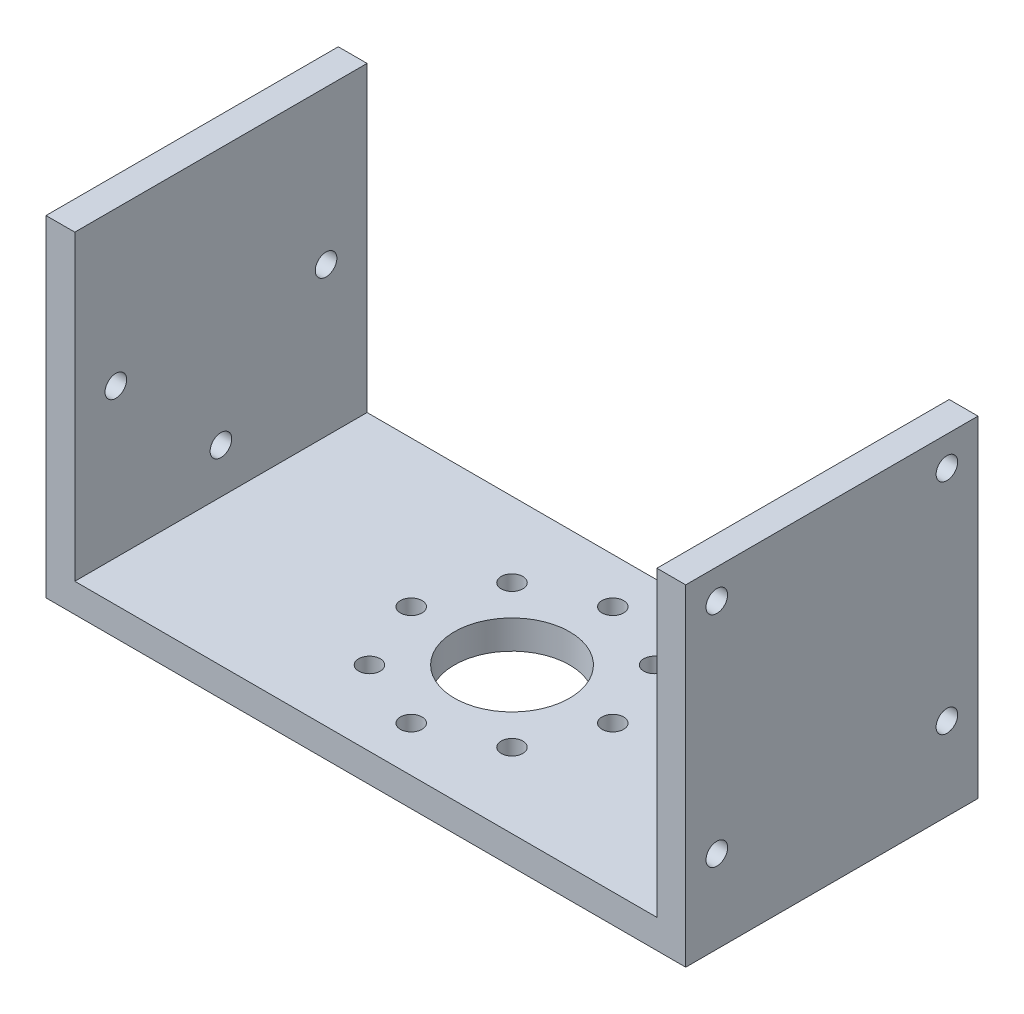
SolidWorks part; units mm, degrees
ref_plane "Front Plane" through (0, 0, 0) normal (0, 0, 1) x (1, 0, 0)
ref_plane "Top Plane" through (0, 0, 0) normal (0, 1, 0) x (1, 0, 0)
ref_plane "Right Plane" through (0, 0, 0) normal (1, 0, 0) x (0, 0, -1)
sketch "Sketch1" plane through (0, 0, 0) normal (0, 1, 0) x (1, 0, 0)
  line L1 (0, 0) -> (44.43, 0)
  line L2 (0, 0) -> (0, 20.3)
  line L3 (0, 20.3) -> (44.43, 20.3)
  line L4 (44.43, 0) -> (44.43, 20.3)
  dimension "D1" = 44.43
  dimension "D2" = 20.3
extrude "YawMount" add sketch "Sketch1" along normal blind 2
sketch "Sketch2" plane through (0, 2, 0) normal (0, 1, 0) x (1, 0, 0)
  line L0 (0, 0) -> (44.43, 0) construction
  line L1 (0, 20.3) -> (2, 20.3)
  line L2 (0, 20.3) -> (0, 0)
  line L3 (0, 0) -> (2, 0)
  line L4 (2, 20.3) -> (2, 0)
  line L6 (44.43, 20.3) -> (42.43, 20.3)
  line L7 (44.43, 20.3) -> (44.43, 0)
  line L8 (44.43, 0) -> (42.43, 0)
  line L9 (42.43, 20.3) -> (42.43, 0)
  dimension "D1" = 2
  dimension "D2" = 2
extrude "BodyConnectors" add sketch "Sketch2" along normal blind 21
sketch "Sketch3" plane through (0, 0, 0) normal (0, -1, 0) x (1, 0, 0)
  line L0 (0, -20.3) -> (0, 0) construction
  line L1 (44.43, -20.3) -> (0, -20.3) construction
  circle A0 centre (22.215, -10.15) radius 4
  point P4 (0, -10.15)
  point P7 (22.215, -20.3)
  dimension "D1" = 8
extrude "Axle-Counterbore" cut sketch "Sketch3" against normal up to surface (2 mm away) up to face at (22.215, 2, -10.15)
sketch "Sketch5" plane through (0, 0, 0) normal (0, -1, 0) x (1, 0, 0)
  line L0 (0, -20.3) -> (0, 0) construction
  line L1 (44.43, -20.3) -> (0, -20.3) construction
  circle A0 centre (15.215, -10.15) radius 0.75
  circle A4 centre (17.2653, -5.2003) radius 0.75
  circle A5 centre (22.215, -3.15) radius 0.75
  circle A6 centre (27.1647, -5.2003) radius 0.75
  circle A7 centre (29.215, -10.15) radius 0.75
  circle A8 centre (27.1647, -15.0997) radius 0.75
  circle A9 centre (22.215, -17.15) radius 0.75
  circle A10 centre (17.2653, -15.0997) radius 0.75
  point P6 (0, -10.15)
  point P24 (22.215, -10.15)
  point P25 (22.215, -20.3)
  dimension "D1" = 1.5
  dimension "D2" = 7
  dimension "D3" = 8
extrude "azel-mountscrews" cut sketch "Sketch5" against normal up to surface (2 mm away) up to face at (22.215, 2, -14.15)
sketch "Sketch6" plane through (2, 0, 0) normal (1, 0, 0) x (0, 0, -1)
  line L0 (0, 23) -> (20.3, 23) construction
  line L3 (0, 2) -> (20.3, 2) construction
  circle A1 centre (10.15, 5.12) radius 0.75
  circle A2 centre (17.45, 12.33) radius 0.75
  circle A3 centre (2.85, 12.33) radius 0.75
  point P5 (10.15, 23)
  dimension "D2" = 1.5
  dimension "D3" = 14.6
  dimension "D4" = 7.21
  dimension "D5" = 7.3
  dimension "D1" = 3.12
extrude "GearSide-Screws" cut sketch "Sketch6" against normal up to surface (2 mm away) up to face at (0, 11.5, -10.15)
sketch "Sketch7" plane through (42.43, 0, 0) normal (-1, 0, 0) x (0, 0, 1)
  line L0 (-20.3, 2) -> (0, 2) construction
  circle A0 centre (-2.16, 5.75) radius 0.75
  circle A1 centre (-18.14, 5.75) radius 0.75
  circle A2 centre (-18.14, 20.95) radius 0.75
  circle A3 centre (-2.16, 20.95) radius 0.75
  point P14 (-10.15, 2)
  dimension "D2" = 1.5
  dimension "D1" = 3.75
  dimension "D3" = 15.98
  dimension "D4" = 7.99
  dimension "D5" = 15.2
extrude "SmoothSide-Screws" cut sketch "Sketch7" against normal up to surface (2 mm away) up to face at (44.43, 11.5, -10.15)
equation "\"srv_w\"= 40.43mm'width of Sain Smart SR319"
equation "\"D1@Sketch1\"=\"srv_w\" + \"mnt_thick\"*2"
equation "\"srv_h\"= 40.61mm'height of Sain Smart SR319"
equation "\"srv_d\"= 20.3mm'depth of Sain Smart SR319"
equation "\"D2@Sketch1\"=\"srv_d\""
equation "\"mnt_thick\"= 2mm'thickness of bracket"
equation "\"D1@YawMount\" = \"mnt_thick\""
equation "\"D2@Sketch2\"=\"mnt_thick\""
equation "\"D1@Sketch2\"=\"mnt_thick\""
equation "\"D5@Sketch6\"=\"D3@Sketch6\"/2"
equation "\"D4@Sketch7\"=\"D3@Sketch7\"/2"
equation "\"clearance\"= 1mm'extra space between bracket and roll rotator servo"
equation "\"D1@Sketch6\"=\"clearance\"+2.12mm"
equation "\"D1@Sketch7\"=\"clearance\"+2.75mm"
